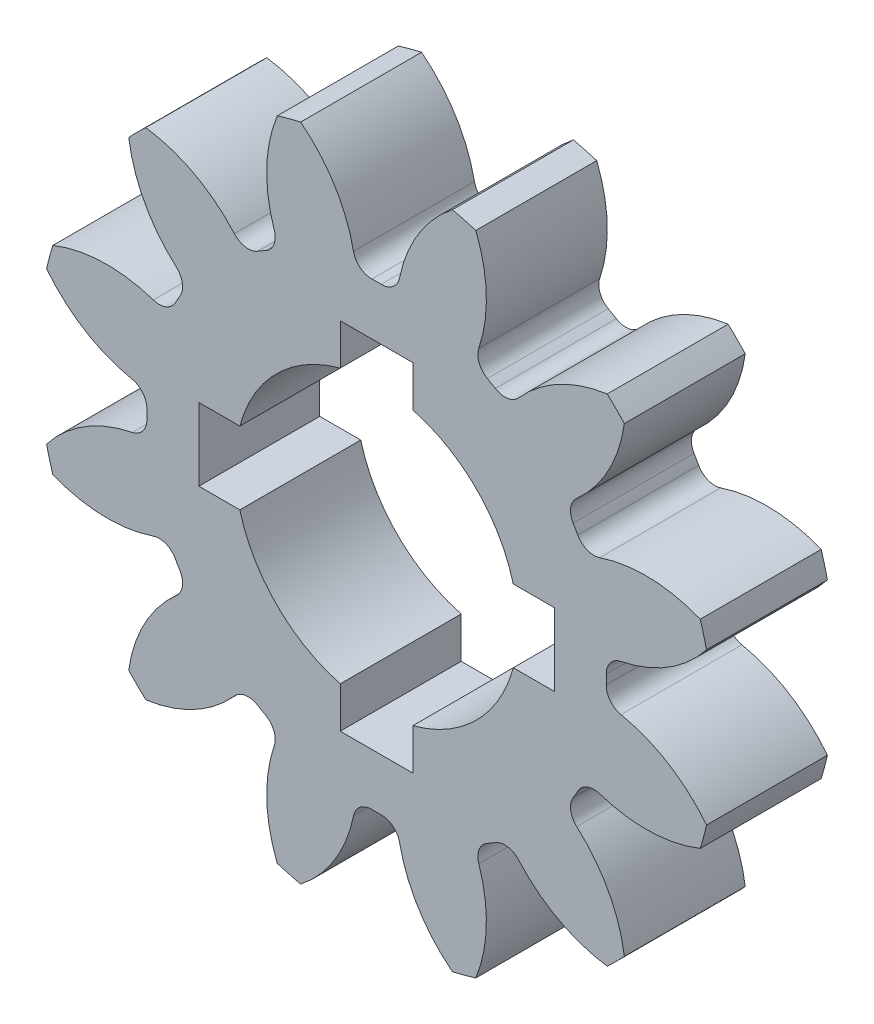
SolidWorks part; units mm, degrees
ref_plane "Front Plane" through (0, 0, 0) normal (0, 0, 1) x (1, 0, 0)
ref_plane "Top Plane" through (0, 0, 0) normal (0, 1, 0) x (1, 0, 0)
ref_plane "Right Plane" through (0, 0, 0) normal (1, 0, 0) x (0, 0, -1)
sketch "Sketch1" plane through (0, 0, 0) normal (0, 0, 1) x (1, 0, 0)
  line L4 (-0.8575, 9.4612) -> (0, 0) construction
  line L5 (0, 0) -> (0, 14) construction
  line L6 (0, 0) -> (3.6235, 13.523) construction
  line L7 (-1.6208, 11.89) -> (0.6878, 13.1053) construction
  line L8 (-1.6208, 11.89) -> (0.3858, 12.1636) construction
  line L11 (1.6208, 11.89) -> (-1.6208, 11.89) construction
  circle A0 centre (0, 0) radius 9.5
  circle A1 centre (0, 0) radius 12 construction
  circle A2 centre (0, 0) radius 14
  arc A3 (-3.1383, 13.6437) -> (-0.8575, 9.4612) centre (-6.8248, 8.9204) cw
  arc A4 (3.1383, 13.6437) -> (0.8575, 9.4612) centre (6.8248, 8.9204) ccw
  point P5 (-12, 0)
  point P6 (-14, 0)
  point P7 (-9.5, 0)
  point P12 (-1.6208, 11.89)
  point P22 (1.6208, 11.89)
  dimension "D5" = 24
  dimension "D1" = 2.5
  dimension "D2" = 2
  dimension "D3" = 20
  dimension "D4" = 3.2416
  dimension "D6" = 15
  dimension "D7" = 0.5
extrude "Boss-Extrude1" add sketch "Sketch1" against normal blind 5 contours A2
extrude "Cut-Extrude1" cut sketch "Sketch1<4>" against normal blind 10 contours A4 A2 A3 A0 region at (0, 12.2045, 0)
sketch "Sketch1<4>" plane through (0, 0, 0) normal (0, 0, 1) x (1, 0, 0) same geometry as "Sketch1"
fillet "Fillet2" radius 0.76 2 edges at (0.8575, 9.4612, -2.5) (-0.8575, 9.4612, -2.5)
ref_axis "Axis1" through (0, 0, 0) along (0, 0, 1)
pattern_circular "CirPattern2" count 12 over 360 about axis through (0, 0, 0) along (0, 0, 1) of "Cut-Extrude1", "Fillet2"
sketch "Sketch2" plane through (0, 0, 0) normal (0, 0, 1) x (1, 0, 0)
  line L0 (-1.5, 5.6528) -> (-1.5, 7.3485)
  line L1 (-1.5, 4.3485) -> (1.5, 4.3485) construction
  line L2 (-1.5, 4.3485) -> (-1.5, 7.3485) construction
  line L3 (-1.5, 7.3485) -> (1.5, 7.3485) construction
  line L4 (1.5, 4.3485) -> (1.5, 7.3485) construction
  line L5 (-1.5, 4.3485) -> (1.5, 7.3485) construction
  line L6 (-1.5, 7.3485) -> (1.5, 4.3485) construction
  line L7 (4.3485, -1.5) -> (7.3485, -1.5) construction
  line L8 (4.3485, -1.5) -> (4.3485, 1.5) construction
  line L9 (4.3485, 1.5) -> (7.3485, 1.5) construction
  line L10 (7.3485, -1.5) -> (7.3485, 1.5) construction
  line L11 (4.3485, -1.5) -> (7.3485, 1.5) construction
  line L12 (4.3485, 1.5) -> (7.3485, -1.5) construction
  line L13 (-1.5, -7.3485) -> (1.5, -7.3485) construction
  line L14 (-1.5, -7.3485) -> (-1.5, -4.3485) construction
  line L15 (-1.5, -4.3485) -> (1.5, -4.3485) construction
  line L16 (1.5, -7.3485) -> (1.5, -4.3485) construction
  line L17 (-1.5, -7.3485) -> (1.5, -4.3485) construction
  line L18 (-1.5, -4.3485) -> (1.5, -7.3485) construction
  line L19 (-7.3485, -1.5) -> (-4.3485, -1.5) construction
  line L20 (-7.3485, -1.5) -> (-7.3485, 1.5) construction
  line L21 (-7.3485, 1.5) -> (-4.3485, 1.5) construction
  line L22 (-4.3485, -1.5) -> (-4.3485, 1.5) construction
  line L23 (-7.3485, -1.5) -> (-4.3485, 1.5) construction
  line L24 (-7.3485, 1.5) -> (-4.3485, -1.5) construction
  line L25 (-1.5, 7.3485) -> (1.5, 7.3485)
  line L26 (1.5, 7.3485) -> (1.5, 5.6528)
  line L27 (5.6528, 1.5) -> (7.3485, 1.5)
  line L28 (7.3485, 1.5) -> (7.3485, -1.5)
  line L29 (7.3485, -1.5) -> (5.6528, -1.5)
  line L30 (1.5, -7.3485) -> (1.5, -5.6528)
  line L31 (1.5, -7.3485) -> (-1.5, -7.3485)
  line L32 (-1.5, -7.3485) -> (-1.5, -5.6528)
  line L33 (-5.6528, -1.5) -> (-7.3485, -1.5)
  line L34 (-7.3485, -1.5) -> (-7.3485, 1.5)
  line L35 (-7.3485, 1.5) -> (-5.6528, 1.5)
  circle A0 centre (0, 0) radius 7.5 construction
  arc A1 (-1.5, 5.6528) -> (-5.6528, 1.5) centre (0, 0) ccw
  arc A2 (5.6528, 1.5) -> (1.5, 5.6528) centre (0, 0) ccw
  arc A3 (1.5, -5.6528) -> (5.6528, -1.5) centre (0, 0) ccw
  arc A4 (-5.6528, -1.5) -> (-1.5, -5.6528) centre (0, 0) ccw
  point P3 (0, 5.8485)
  point P8 (5.8485, 0)
  point P13 (0, -5.8485)
  point P18 (-5.8485, 0)
  dimension "D1" = 15
  dimension "D2" = 3
extrude "Cut-Extrude2" cut sketch "Sketch2" against normal up to surface (5 mm away) up to face at (0, 0, -5)
equation "\"backlash\"= 0.1mm"
equation "\"module\"= 2mm"
equation "\"pressureAngle\"= 20deg"
equation "\"width\"= 10mm"
equation "\"D1@Sketch1\"= 1.25 * \"module\""
equation "\"D2@Sketch1\"=\"module\""
equation "\"D5@Sketch1\"=\"module\"*\"numberOfTeeth\""
equation "\"D1@Boss-Extrude1\"=\"width\"-5"
equation "\"D3@Sketch1\"=\"pressureAngle\""
equation "\"D1@Cut-Extrude1\"=\"width\""
equation "\"D1@CirPattern2\"=\"numberOfTeeth\""
equation "\"D1@Fillet2\"=0.38*\"module\""
equation "\"D4@Sketch1\"=pi*\"module\"/2+\"backlash\""
equation "\"numberOfTeeth\"= 12"
equation "\"D6@Sketch1\"=180/\"numberOfTeeth\""
equation "\"toothTipProfile\"= 1mm"
equation "\"D7@Sketch1\"=\"toothTipProfile\"/2"
equation "\"lengthOverallRack\"= pi * \"module\" * \"numberOfTeethRack\""
equation "\"numberOfTeethRack\"= 20"
